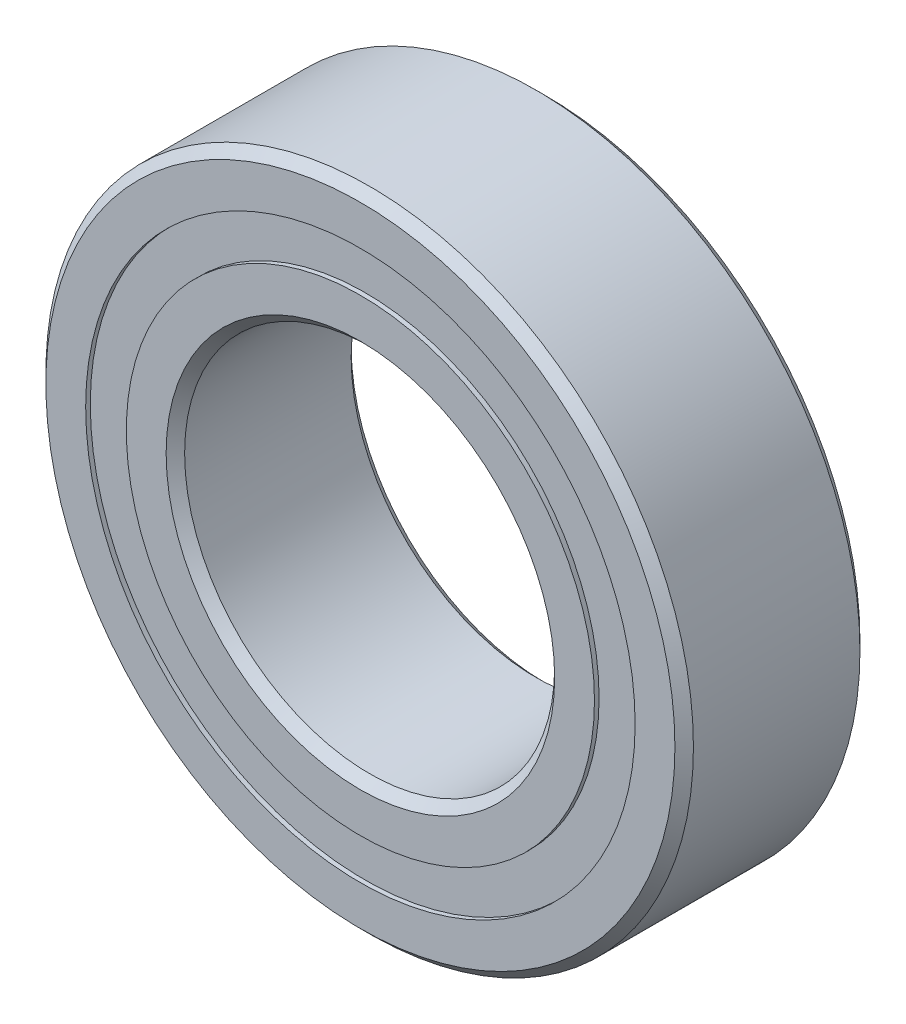
SolidWorks part; units mm, degrees
ref_plane "Front Plane" through (0, 0, 0) normal (0, 0, 1) x (1, 0, 0)
ref_plane "Top Plane" through (0, 0, 0) normal (0, 1, 0) x (1, 0, 0)
ref_plane "Right Plane" through (0, 0, 0) normal (1, 0, 0) x (0, 0, -1)
sketch "Sketch1" plane through (0, 0, 0) normal (1, 0, 0) x (0, 0, -1)
  line L0 (-2, 0) -> (2, 0) construction
  line L1 (0, 7) -> (0, -7) construction
  line L2 (1.8, 7) -> (-1.8, 7)
  line L3 (-1.8, 7) -> (-2, 6.8)
  line L4 (-2, 6.8) -> (-2, 5.9396)
  line L5 (-2, 5.9396) -> (-0.8889, 5.9396)
  line L6 (2, 5.9396) -> (0.8889, 5.9396)
  line L7 (2, 6.8) -> (2, 5.9396)
  line L8 (1.8, 7) -> (2, 6.8)
  line L9 (0, 7) -> (0, 5.5) construction
  line L10 (0, 5.5) -> (0, 4) construction
  arc A0 (-0.8889, 5.9396) -> (0.8889, 5.9396) centre (0, 5.5) cw
  point P14 (0, 4)
  dimension "Width" = 4
  dimension "OD" = 14
  dimension "D1" = 45
  dimension "D2" = 0.2
  dimension "Shaft Dia" = 8
  dimension "D3" = 1.7778
  dimension "D4" = 0.4396
revolve "Revolve1" add sketch "Sketch1" angle 360 about L0
sketch "Sketch3" plane through (0, 0, 0) normal (1, 0, 0) x (0, 0, -1)
  line L0 (-2, 5.0604) -> (-0.8889, 5.0604)
  line L1 (0, 7) -> (0, -7) construction
  line L2 (-2, 6.8) -> (-2, 5.9396) construction
  line L3 (-2, 5.0604) -> (-2, 4.2)
  line L4 (-1.8, 7) -> (-2, 6.8) construction
  line L5 (-2, 4.2) -> (-1.8, 4)
  line L6 (-1.8, 4) -> (1.8, 4)
  line L7 (1.8, 7) -> (1.8, -7) construction
  line L8 (1.8, 4) -> (2, 4.2)
  line L9 (2, -6.8) -> (2, 6.8) construction
  line L10 (2, 4.2) -> (2, 5.0604)
  line L11 (2, 5.0604) -> (0.8889, 5.0604)
  line L13 (1.8, 7) -> (2, 6.8) construction
  arc A0 (0.8889, 5.9396) -> (-0.8889, 5.9396) centre (0, 5.5) ccw construction
  arc A1 (0.8889, 5.0604) -> (-0.8889, 5.0604) centre (0, 5.5) cw
revolve "Revolve3" add sketch "Sketch3" angle 360 about L0
sketch "Sketch4" plane through (0, 0, 0) normal (1, 0, 0) x (0, 0, -1)
  line L0 (-0.9916, 5.5) -> (0.9916, 5.5)
  arc A2 (-0.9916, 5.5) -> (0.9916, 5.5) centre (0, 5.5) cw
  arc A3 (0.8889, 5.9396) -> (-0.8889, 5.9396) centre (0, 5.5) ccw construction
revolve "Revolve4" add sketch "Sketch4" angle 360 about L0
ref_axis "Axis1" through (0, 0, -2) along (0, 0, 1)
pattern_circular "CirPattern1" count 12 every 30 about axis through (0, 0, -2) along (0, 0, 1) of bodies 104
sketch "Sketch5" plane through (0, 0, 0) normal (1, 0, 0) x (0, 0, -1)
  line L0 (-2, 5.9396) -> (-0.8889, 5.9396) construction
  line L1 (-1.9, 5.9396) -> (-0.9916, 5.9396)
  line L2 (-1.9, 5.9396) -> (-1.9, 5.0604)
  line L3 (-1.9, 5.0604) -> (-0.9916, 5.0604)
  line L4 (-0.9916, 5.9396) -> (-0.9916, 5.0604)
  line L5 (-2, 5.0604) -> (-0.8889, 5.0604) construction
  line L6 (2, 5.9396) -> (0.8889, 5.9396) construction
  line L7 (1.9, 5.9396) -> (0.9916, 5.9396)
  line L8 (1.9, 5.9396) -> (1.9, 5.0604)
  line L9 (1.9, 5.0604) -> (0.9916, 5.0604)
  line L10 (0.9916, 5.9396) -> (0.9916, 5.0604)
  line L11 (2, 5.0604) -> (0.8889, 5.0604) construction
  line L12 (-1.8, 7) -> (-2, 6.8) construction
  point P18 (-1.9, 6.9)
revolve "Revolve5" add sketch "Sketch5" angle 360 about L0
sketch "Sketch6" plane through (0, 0, 0) normal (1, 0, 0) x (0, 0, -1)
  line L0 (2, 0) -> (-2, 0) construction
  line L1 (2, 5.9396) -> (0.9, 5.9396)
  line L2 (2, 5.9396) -> (2, 9.5)
  line L3 (2, 9.5) -> (0.9, 9.5)
  line L4 (0.9, 5.9396) -> (0.9, 9.5)
  dimension "Th" = 1.1
  dimension "Flange OD" = 19
revolve "Revolve6" [suppressed] add sketch "Sketch6" angle 360 about L0
equation "\"D2@Sketch1\" = \"Width@Sketch1\"*.05"
equation "\"D3@Sketch1\" = \"Width@Sketch1\"/2.25"
equation "\"D4@Sketch1\" = (((\"OD@Sketch1\"-\"Width@Sketch1\")/2)/3.25)/3.5"
equation "\"D2@CirPattern1\" = 360/\"Balls@CirPattern1\""
